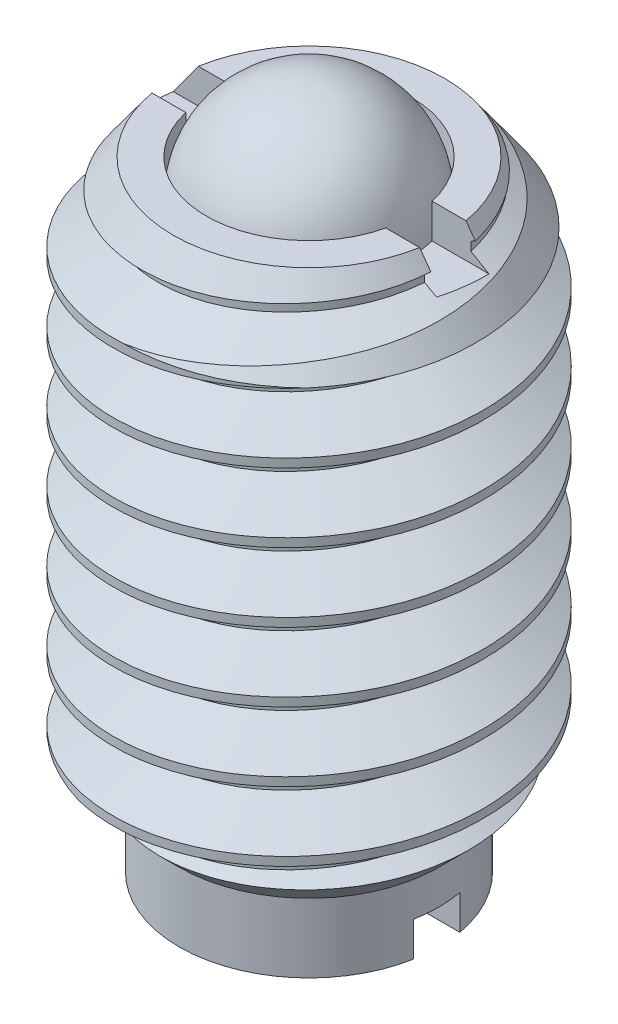
SolidWorks part; units mm, degrees
ref_plane "Front" through (0, 0, 0) normal (0, 0, 1) x (1, 0, 0)
ref_plane "Top" through (0, 0, 0) normal (0, 1, 0) x (1, 0, 0)
ref_plane "Right" through (0, 0, 0) normal (1, 0, 0) x (0, 0, -1)
sketch "Sketch24" plane through (0, 0, 0) normal (1, 0, 0) x (0, 0, -1)
  line L0 (1.4224, 2.3749) -> (-1.4224, 2.3749) construction
  line L1 (0, 2.3749) -> (1.4224, 2.3749)
  line L2 (0, 2.3749) -> (0, -2.3749)
  line L3 (0, -2.3749) -> (1.4224, -2.3749)
  line L4 (1.4224, 2.3749) -> (1.4224, -2.3749)
  point P5 (1.4224, -0.0064)
  dimension "D1" = 2.3813
  dimension "Body Length" = 4.7498
  dimension "Screw Dia" = 2.8448
revolve "Revolve1" add sketch "Sketch24" angle 360 about L2
sketch "Sketch37" plane through (0, 2.3749, 0) normal (0, 1, 0) x (1, 0, 0)
  circle A1 centre (0, 0) radius 1.4224
  circle A2 centre (0, 0) radius 1.4224
  dimension "D1" = 0
curve "Helix/Spiral1" pitch 0.5292 height 5.279 turns 9.976 parameters "pitch"=0.5292
sketch "Sketch38" plane through (0, 0, 0) normal (1, 0, 0) x (0, 0, -1)
  line L0 (-1.4224, 2.8379) -> (-1.4224, 2.3749)
  line L1 (-1.4224, 2.8379) -> (-1.0787, 2.6395)
  line L2 (-1.0787, 2.6395) -> (-1.0787, 2.5733)
  line L3 (-1.0787, 2.5733) -> (-1.4224, 2.3749)
  line L4 (-1.0787, 2.6064) -> (-1.4224, 2.6064) construction
  line L5 (-1.2505, 2.7387) -> (-1.2505, 2.4741) construction
  line L6 (1.4224, 2.3749) -> (-1.4224, 2.3749) construction
  line L7 (0, 0) -> (0, 2.3749) construction
  dimension "D1" = 0.0661
  dimension "D2" = 0.2646
  dimension "D3" = 60
  dimension "D4" = 0.3437
  dimension "D5" = 1.0787
  dimension "D6" = 0.1719
sweep "Cut-Sweep1" cut profiles "Sketch38" path "Helix/Spiral1"
sketch "Sketch26" plane through (0, 0, 0) normal (1, 0, 0) x (0, 0, -1)
  line L0 (0, -1.8999) -> (0, 2.3749)
  line L1 (0, 2.3749) -> (0, -2.3749) construction
  line L2 (0, 2.3749) -> (0.7874, 2.3749)
  line L3 (0.7874, 2.3749) -> (0.7874, -1.8999)
  line L5 (0.7874, -1.8999) -> (0, -1.8999)
  line L7 (0.7874, 2.3749) -> (-0.7874, 2.3749) construction
  line L8 (1.4224, 2.3749) -> (-1.4224, 2.3749) construction
  dimension "D1" = 0.475
  dimension "Ball Dia" = 1.5748
revolve "Cut-Revolve10" cut sketch "Sketch26" angle 360 about L0
sketch "Sketch31" plane through (0, 0, 0) normal (1, 0, 0) x (0, 0, -1)
  line L0 (1.4224, -2.3749) -> (0.9957, -2.3749)
  line L1 (1.4224, 2.3749) -> (1.4224, -2.3749) construction
  line L2 (0.9957, -2.3749) -> (0.9957, -1.8457)
  line L3 (0, 0) -> (0, -14.5366) construction
  line L4 (0.9957, -1.8457) -> (1.4224, -1.419)
  line L5 (0, 0) -> (1.4224, 0) construction
  line L14 (1.4224, 2.3749) -> (1.0414, 2.3749)
  line L15 (0, 2.3749) -> (1.4224, 2.3749) construction
  line L16 (1.0414, 2.3749) -> (1.4224, 1.8457)
  line L17 (1.4224, 1.8457) -> (1.4224, 2.3749)
  line L18 (1.4224, -1.419) -> (1.4224, -2.3749)
  dimension "D1" = 0.254
  dimension "D2" = 45
  dimension "D3" = 0.5292
  dimension "D4" = 0.9957
revolve "Cut-Revolve13" cut sketch "Sketch31" angle 360 about L2
sketch "Sketch28" plane through (0, 0, 0) normal (1, 0, 0) x (0, 0, -1)
  line L0 (0.9957, -2.1103) -> (0.1778, -2.1103) construction
  line L1 (-0.1778, -2.3749) -> (0.1778, -2.3749)
  line L2 (-0.1778, -2.3749) -> (-0.1778, -2.1103)
  line L3 (-0.1778, -2.1103) -> (0.1778, -2.1103)
  line L4 (0.1778, -2.3749) -> (0.1778, -2.1103)
  line L5 (1.4224, 2.3749) -> (-1.4224, 2.3749) construction
  line L6 (-0.1778, 2.3749) -> (0.1778, 2.3749)
  line L7 (-0.1778, 2.3749) -> (-0.1778, 2.1103)
  line L8 (-0.1778, 2.1103) -> (0.1778, 2.1103)
  line L9 (0.1778, 2.3749) -> (0.1778, 2.1103)
  line L10 (0.9957, -2.3749) -> (0.9957, -1.8457) construction
  dimension "D1" = 0.3556
extrude "Cut-Extrude11" cut sketch "Sketch28" against normal through all and the other way through all
sketch "Sketch27" plane through (0, 0, 0) normal (1, 0, 0) x (0, 0, -1)
  line L0 (0, 2.3749) -> (0, -2.3749) construction
  line L1 (0.7874, 2.3749) -> (0.7874, -1.8999) construction
  line L2 (0, -2.3749) -> (0, 1.3081) construction
  line L3 (0, 2.8829) -> (0, 1.3081)
  circle A0 centre (0, 2.0955) radius 0.7874 construction
  arc A1 (0, 2.8829) -> (0, 1.3081) centre (0, 2.0955) cw
  dimension "Ball Projection" = 0.508
revolve "Revolve2" add sketch "Sketch27" angle 360 about L3
ref_plane "Plane1" [suppressed] through (-1.4224, 0, 0) normal (1, 0, 0) x (0, 0, -1)
sketch "Sketch21" [suppressed] plane through (-1.4224, 0, 0) normal (1, 0, 0) x (0, 0, -1)
  line L0 (0, -1.7183) -> (0, -3.2804) construction
  line L2 (1.4224, 2.3749) -> (-1.4224, 2.3749) construction
  line L3 (0, 2.3749) -> (0, -2.3749) construction
  ellipse E0 centre (0, -0.4661) end of major axis (0, 0.4585) minor radius 0.7112
  dimension "D5" = 1.4224
  dimension "D6" = 1.8491
  dimension "D7" = 1.9164
sketch "Sketch41" [suppressed] plane through (-1.4224, 0, 0) normal (1, 0, 0) x (0, 0, -1)
  ellipse E1 centre (0, -0.4661) end of major axis (0, 0.4585) minor radius 0.7112
  ellipse E2 centre (0, -0.4661) end of major axis (0, 0.4585) minor radius 0.7112
  dimension "D1" = 0
sketch "Sketch43" [suppressed] plane through (0, 0, 0) normal (1, 0, 0) x (0, 0, -1)
  ellipse E1 centre (0, -0.4661) end of major axis (0, 0.4585) minor radius 0.7112
  ellipse E2 centre (0, -0.4661) end of major axis (0, 0.4585) minor radius 0.7112
  dimension "D1" = 0
extrude "Extrude9" [suppressed] cut sketch "Sketch43" against normal through all
sketch "Sketch44" [suppressed] plane through (0, 0, 0) normal (1, 0, 0) x (0, 0, -1)
  ellipse E1 centre (0, -0.4661) end of major axis (0, 0.4585) minor radius 0.7112
  ellipse E2 centre (0, -0.4661) end of major axis (0, 0.4585) minor radius 0.7112
  dimension "D1" = 0
extrude "Extrude10" [suppressed] add sketch "Sketch44" against normal blind 1.0787 separate body
dome "Dome1" [suppressed] faces to dome 1 distance 0.1719 parameters "D1"=0.1719
sketch "Sketch45" plane through (0, 0, 0) normal (0, 1, 0) x (1, 0, 0)
  circle A0 centre (0, 0) radius 0.7874
  arc A1 (-0.7671, -0.1778) -> (0.7671, -0.1778) centre (0, 0) ccw construction
extrude "Extrude11" [suppressed] cut sketch "Sketch45" against normal through all and the other way through all
equation "\"D1@Sketch26\" = \"Body Length@Sketch24\"*.1"
equation "\"D1@Sketch28\" = \"Screw Dia@Sketch24\"/8"
equation "\"D1@Sketch38\" = \"pitch@Helix/Spiral1\"*.125"
equation "\"D2@Sketch38\" = \"pitch@Helix/Spiral1\"*.50"
equation "\"D3@Helix/Spiral1\" = \"Body Length@Sketch24\"+\"pitch@Helix/Spiral1\""
equation "\"D3@Sketch31\" = \"pitch@Helix/Spiral1\""
equation "\"D4@Sketch31\" = (\"Screw Dia@Sketch24\"/2)*.7"
equation "\"D5@Sketch21\" = \"Screw Dia@Sketch24\"*.50"
equation "\"D6@Sketch21\" = \"D5@Sketch21\"*1.3"
equation "\"D7@Sketch21\" = \"pitch@Helix/Spiral1\"*3.62154"
equation "\"D1@Sketch24\" = \"pitch@Helix/Spiral1\"*4.50"
equation "\"D1@Plane1\" = \"Screw Dia@Sketch24\"/2"
equation "\"D1@Extrude10\" = \"D5@Sketch38\""
equation "\"D1@Dome1\" = \"D6@Sketch38\""
